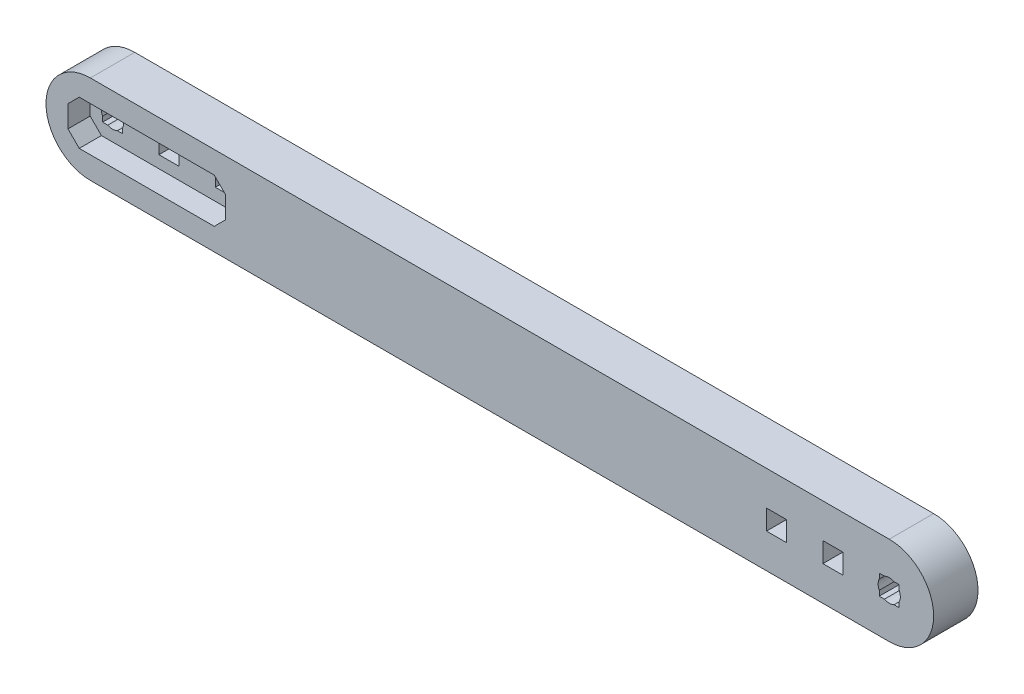
SolidWorks part; units mm, degrees
ref_plane "Front Plane" through (0, 0, 0) normal (0, 0, 1) x (1, 0, 0)
ref_plane "Top Plane" through (0, 0, 0) normal (0, 1, 0) x (1, 0, 0)
ref_plane "Right Plane" through (0, 0, 0) normal (1, 0, 0) x (0, 0, -1)
sketch "Sketch1" plane through (0, 0, 0) normal (0, 0, 1) x (1, 0, 0)
  line L0 (0, 10) -> (180, 10)
  line L1 (180, -10) -> (0, -10)
  circle A0 centre (0, 0) radius 2.5
  circle A1 centre (180, 0) radius 2.5
  arc A2 (0, -10) -> (0, 10) centre (0, 0) cw
  arc A3 (180, -10) -> (180, 10) centre (180, 0) ccw
  point P9 (-10, 0)
  dimension "D2" = 5
  dimension "D3" = 10
  dimension "D1" = 180
extrude "Boss-Extrude1" add sketch "Sketch1" along normal blind 10
sketch "Sketch2" plane through (0, 0, 10) normal (0, 0, 1) x (1, 0, 0)
  line L0 (27.91, -5) -> (30.45, -2.46)
  line L1 (30.45, -2.46) -> (30.45, 2.46)
  line L2 (27.91, -5) -> (-2.51, -5)
  line L3 (-5.05, -2.46) -> (-5.05, 2.46)
  line L4 (27.91, 5) -> (-2.51, 5)
  line L5 (30.45, -5) -> (-5.05, 5) construction
  line L6 (-5.05, -5) -> (30.45, 5) construction
  line L7 (30.45, 2.46) -> (27.91, 5)
  line L8 (-5.05, 2.46) -> (-2.51, 5)
  line L9 (-2.51, -5) -> (-5.05, -2.46)
  line L10 (27.65, 2.25) -> (23.15, 2.25)
  line L11 (27.65, 2.25) -> (27.65, -2.25)
  line L12 (27.65, -2.25) -> (23.15, -2.25)
  line L13 (23.15, 2.25) -> (23.15, -2.25)
  line L14 (27.65, 2.25) -> (23.15, -2.25) construction
  line L15 (27.65, -2.25) -> (23.15, 2.25) construction
  line L16 (14.95, 2.25) -> (10.45, 2.25)
  line L17 (14.95, 2.25) -> (14.95, -2.25)
  line L18 (14.95, -2.25) -> (10.45, -2.25)
  line L19 (10.45, 2.25) -> (10.45, -2.25)
  line L20 (14.95, 2.25) -> (10.45, -2.25) construction
  line L21 (14.95, -2.25) -> (10.45, 2.25) construction
  line L22 (2.25, 2.25) -> (-2.25, 2.25)
  line L23 (2.25, 2.25) -> (2.25, -2.25)
  line L24 (2.25, -2.25) -> (-2.25, -2.25)
  line L25 (-2.25, 2.25) -> (-2.25, -2.25)
  line L26 (2.25, 2.25) -> (-2.25, -2.25) construction
  line L27 (2.25, -2.25) -> (-2.25, 2.25) construction
  circle A0 centre (0, 0) radius 2.5
  point P0 (25.4, 0)
  point P2 (12.7, 0)
  point P18 (12.7, 0)
  point P23 (0, 0)
  point P30 (0, 0)
  circle M10 centre (0, 0) radius 2.5
  dimension "D12" = 5
  dimension "D1" = 2.54
  dimension "D2" = 2.54
  dimension "D3" = 2.54
  dimension "D4" = 2.54
  dimension "D5" = 2.54
  dimension "D6" = 2.54
  dimension "D7" = 2.54
  dimension "D8" = 2.54
  dimension "D9" = 12.7
  dimension "D10" = 12.7
  dimension "D11" = 4.5
  dimension "D13" = 10
  dimension "D14" = 35.5
extrude "Cut-Extrude1" cut sketch "Sketch2" against normal blind 10 contours L22 L25 L24 L23 | A0 | L19 L18 L17 L16 | L13 L12 L11 L10
extrude "Cut-Extrude2" cut sketch "Sketch2<3>" against normal blind 5 contours L9 L2 L0 L1 L7 L4 L8 L3 L25 L22 L23 L24 L19 L16 L17 L18 L13 L10 L11 L12 M10 region at (12.7, -4.6312, 10)
sketch "Sketch2<3>" plane through (0, 0, 10) normal (0, 0, 1) x (1, 0, 0) same geometry as "Sketch2"
sketch "Sketch3" plane through (0, 0, 0) normal (0, 0, -1) x (-1, 0, 0)
  line L0 (-152.09, -5) -> (-149.55, -2.46)
  line L1 (-149.55, -2.46) -> (-149.55, 2.46)
  line L2 (-152.09, -5) -> (-182.51, -5)
  line L3 (-185.05, -2.46) -> (-185.05, 2.46)
  line L4 (-152.09, 5) -> (-182.51, 5)
  line L5 (-149.55, -5) -> (-185.05, 5) construction
  line L6 (-185.05, -5) -> (-149.55, 5) construction
  line L7 (-149.55, 2.46) -> (-152.09, 5)
  line L8 (-185.05, 2.46) -> (-182.51, 5)
  line L9 (-182.51, -5) -> (-185.05, -2.46)
  line L10 (-152.35, 2.25) -> (-156.85, 2.25)
  line L11 (-152.35, 2.25) -> (-152.35, -2.25)
  line L12 (-152.35, -2.25) -> (-156.85, -2.25)
  line L13 (-156.85, 2.25) -> (-156.85, -2.25)
  line L14 (-152.35, 2.25) -> (-156.85, -2.25) construction
  line L15 (-152.35, -2.25) -> (-156.85, 2.25) construction
  line L16 (-165.05, 2.25) -> (-169.55, 2.25)
  line L17 (-165.05, 2.25) -> (-165.05, -2.25)
  line L18 (-165.05, -2.25) -> (-169.55, -2.25)
  line L19 (-169.55, 2.25) -> (-169.55, -2.25)
  line L20 (-165.05, 2.25) -> (-169.55, -2.25) construction
  line L21 (-165.05, -2.25) -> (-169.55, 2.25) construction
  line L22 (-177.75, 2.25) -> (-182.25, 2.25)
  line L23 (-177.75, 2.25) -> (-177.75, -2.25)
  line L24 (-177.75, -2.25) -> (-182.25, -2.25)
  line L25 (-182.25, 2.25) -> (-182.25, -2.25)
  line L26 (-177.75, 2.25) -> (-182.25, -2.25) construction
  line L27 (-177.75, -2.25) -> (-182.25, 2.25) construction
  circle A0 centre (-180, 0) radius 2.5
  point P0 (-154.6, 0)
  point P2 (-167.3, 0)
  point P18 (-167.3, 0)
  point P23 (-180, 0)
  point P30 (-180, 0)
  circle M13 centre (-180, 0) radius 2.5
  dimension "D12" = 5
  dimension "D1" = 2.54
  dimension "D2" = 2.54
  dimension "D3" = 2.54
  dimension "D4" = 2.54
  dimension "D5" = 2.54
  dimension "D6" = 2.54
  dimension "D7" = 2.54
  dimension "D8" = 2.54
  dimension "D9" = 12.7
  dimension "D10" = 12.7
  dimension "D11" = 4.5
  dimension "D13" = 10
  dimension "D14" = 35.5
extrude "Cut-Extrude3" cut sketch "Sketch3" against normal blind 10 contours L19 L18 L17 L16 | L13 L12 L11 L10 | A0 | L23 L24 L25 L22
extrude "Cut-Extrude4" cut sketch "Sketch3<3>" against normal blind 5 contours L9 L2 L0 L1 L7 L4 L8 L3 L25 L22 L23 L24 L19 L16 L17 L18 L13 L10 L11 L12 M13 region at (167.3, -4.6312, 0)
sketch "Sketch3<3>" plane through (0, 0, 0) normal (0, 0, -1) x (-1, 0, 0) same geometry as "Sketch3"
